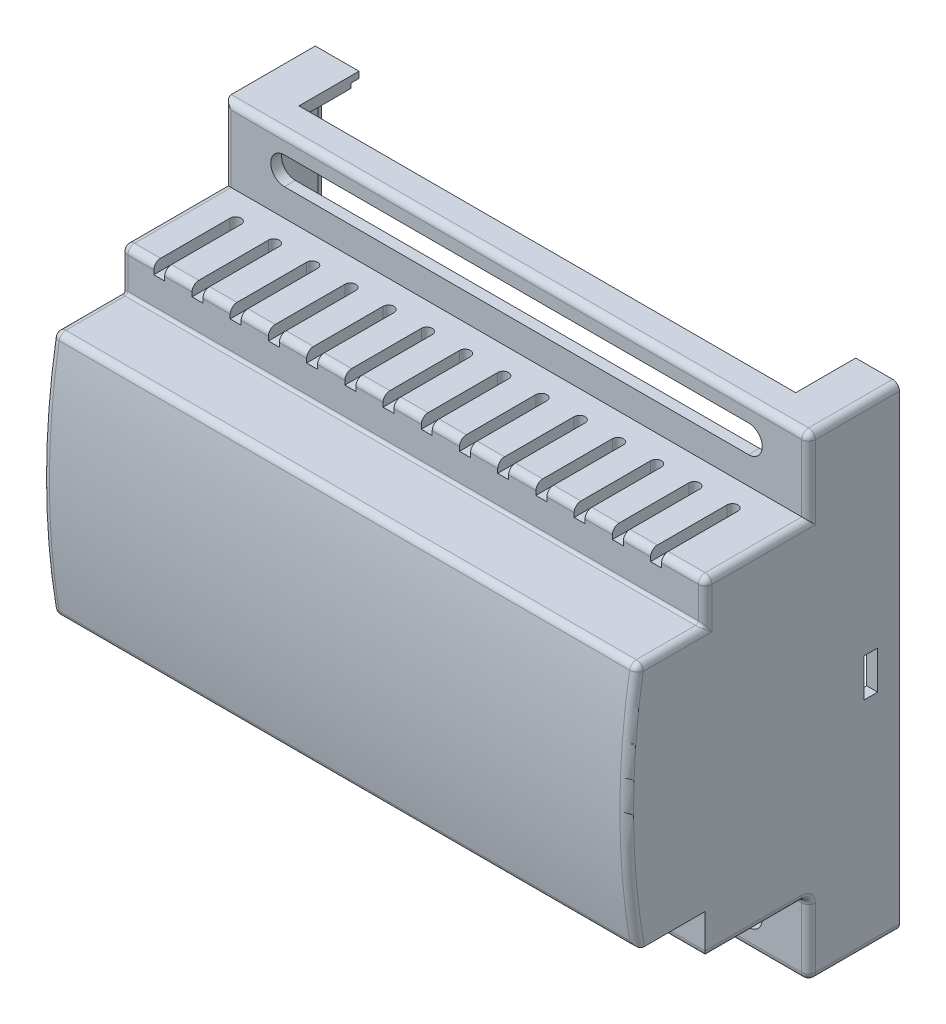
SolidWorks part; units mm, degrees
ref_plane "Alzado" through (0, 0, 0) normal (0, 0, 1) x (1, 0, 0)
ref_plane "Planta" through (0, 0, 0) normal (0, 1, 0) x (1, 0, 0)
ref_plane "Vista lateral" through (0, 0, 0) normal (1, 0, 0) x (0, 0, -1)
sketch "Sketch1" plane through (0, 0, 0) normal (1, 0, 0) x (0, 0, -1)
  line L0 (0, -43.5) -> (0, 43.5)
  line L1 (0, 43.5) -> (-16.65, 43.5)
  line L2 (-16.65, 43.5) -> (-16.65, 30)
  line L3 (-16.65, 30) -> (-35.59, 30)
  line L4 (-35.59, 30) -> (-35.59, 22.5)
  line L5 (-35.59, 22.5) -> (-48, 22.5)
  line L7 (55, 0) -> (-55, 0) construction
  line L8 (-35.59, -22.5) -> (-48, -22.5)
  line L9 (-35.59, -30) -> (-35.59, -22.5)
  line L10 (-16.65, -30) -> (-35.59, -30)
  line L11 (-16.65, -43.5) -> (-16.65, -30)
  line L12 (0, -43.5) -> (-16.65, -43.5)
  arc A1 (-48, 22.5) -> (-48, -22.5) centre (79.6725, 0) ccw
  point P12 (-48, 0)
  point P17 (0, 0)
  dimension "D7" = 259.28
  dimension "D1" = 87
  dimension "D2" = 16.65
  dimension "D3" = 35.59
  dimension "D4" = 48
  dimension "D5" = 60
  dimension "D6" = 45
extrude "Boss-Extrude3" add sketch "Sketch1" along normal blind 107
shell "Shell3" thickness 2 removed face at (53.5, 0, 0)
fillet "Fillet3" radius 1.25 26 edges at (107, 0, 49.9675) (53.5, -22.5, 48) (0, 0, 49.9675) (53.5, 22.5, 48) (107, -36.75, 16.65) (0, -36.75, 16.65) (53.5, -30, 35.59) (107, -30, 26.12) (53.5, -30, 16.65) (0, -30, 26.12) (0, -26.25, 35.59) (0, -22.5, 41.795) (0, 22.5, 41.795) (0, 26.25, 35.59) (0, 30, 26.12) (0, 36.75, 16.65) (53.5, 43.5, 16.65) (107, 43.5, 8.325) (107, 36.75, 16.65) (107, 30, 26.12) (53.5, 30, 35.59) (107, 26.25, 35.59) (107, 22.5, 41.795) (0, -43.5, 8.325) (107, -43.5, 8.325) (53.5, -43.5, 16.65)
sketch "Sketch5" plane through (107, 0, 0) normal (1, 0, 0) x (0, 0, -1)
  line L0 (0, 0) -> (-48.7175, 0) construction
  line L1 (0, -42.25) -> (0, 42.25) construction
  line L2 (-4, 3.5) -> (-6.5, 3.5)
  line L3 (-4, 3.5) -> (-4, -3.5)
  line L4 (-4, -3.5) -> (-6.5, -3.5)
  line L5 (-6.5, 3.5) -> (-6.5, -3.5)
  line L6 (-4, 3.5) -> (-6.5, -3.5) construction
  line L7 (-4, -3.5) -> (-6.5, 3.5) construction
  arc A0 (-46.9467, 21.25) -> (-46.7305, -22.5) centre (79.6725, 0) ccw construction
  point P7 (-5.25, 0)
  point P14 (-5.25, -3.5)
  dimension "D1" = 4
  dimension "D2" = 7
  dimension "D3" = 2.5
extrude "Cut-Extrude3" cut sketch "Sketch5" against normal through all
sketch "Sketch6" plane through (0, -43.5, 0) normal (0, -1, 0) x (1, 0, 0)
  line L0 (105.75, 0) -> (1.25, 0) construction
  line L1 (99, -11) -> (8, -11)
  line L2 (99, -11) -> (99, 11)
  line L3 (99, 11) -> (8, 11)
  line L4 (8, -11) -> (8, 11)
  line L5 (99, -11) -> (8, 11) construction
  line L6 (99, 11) -> (8, -11) construction
  point P0 (53.5, 0)
  dimension "D1" = 91
  dimension "D2" = 11
extrude "Cut-Extrude4" cut sketch "Sketch6" against normal through all
sketch "Sketch7" plane through (0, 0, 16.65) normal (0, 0, 1) x (1, 0, 0)
  line L0 (11, -37.5) -> (96, -37.5) construction
  line L1 (11, -35) -> (96, -35)
  line L2 (11, -40) -> (96, -40)
  line L3 (96, 37.52) -> (11, 37.52) construction
  line L4 (96, 35) -> (11, 35)
  line L5 (96, 40.04) -> (11, 40.04)
  line L6 (53.5, 42.25) -> (53.5, -43.5) construction
  line L7 (105.75, 42.25) -> (1.25, 42.25) construction
  line L8 (105.75, -43.5) -> (1.25, -43.5) construction
  arc A0 (11, -35) -> (11, -40) centre (11, -37.5) ccw
  arc A1 (96, -40) -> (96, -35) centre (96, -37.5) ccw
  arc A2 (96, 35) -> (96, 40.04) centre (96, 37.52) ccw
  arc A3 (11, 40.04) -> (11, 35) centre (11, 37.52) ccw
  point P2 (53.5, -37.5)
  point P10 (53.5, 37.52)
  dimension "D5" = 2.52
  dimension "D6" = 2.5
  dimension "D1" = 85
  dimension "D2" = 35
  dimension "D3" = 85
  dimension "D4" = 35
extrude "Cut-Extrude5" cut sketch "Sketch7" against normal blind 3
fillet "Fillet4" radius 0.5 30 edges at (2, -20.5, 39.9502) (2, -34.75, 14.65) (105, -20.5, 39.9502) (106.6339, 22.1339, 35.2239) (0.3661, 22.1339, 35.2239) (53.5, -20.5, 46.3105) (53.5, 20.5, 46.3105) (53.5, 22.5, 35.59) (53.5, 28, 33.59) (53.5, 28, 14.65) (105, 0, 47.9675) (105, 20.5, 39.9502) (105, 24.25, 33.59) (105, 28, 24.12) (105, 34.75, 14.65) (105, 41.5, 7.325) (2, 41.5, 7.325) (2, 34.75, 14.65) (2, 28, 24.12) (2, 24.25, 33.59) (2, 20.5, 39.9502) (2, 0, 47.9675) (2, -24.25, 33.59) (53.5, -28, 14.65) (105, -34.75, 14.65) (105, -28, 24.12) (105, -24.25, 33.59) (53.5, -28, 33.59) (2, -28, 24.12) (53.5, -20.5, 33.59)
sketch "Sketch8" plane through (0, -30, 0) normal (0, -1, 0) x (1, 0, 0)
  line L0 (107, 35.59) -> (1.25, 35.59) construction
  line L1 (6, 35.59) -> (8, 35.59)
  line L2 (6, 35.59) -> (6, 21.59)
  line L4 (8, 35.59) -> (8, 21.59)
  line L5 (8, 0) -> (1.25, 0) construction
  line L8 (53.5, 49.9675) -> (53.5, 0) construction
  line L9 (105.75, 49.9675) -> (1.25, 49.9675) construction
  line L11 (0, 17.9) -> (0, 34.34) construction
  line L12 (13, 35.59) -> (13, 21.59)
  line L13 (15, 35.59) -> (15, 21.59)
  line L14 (13, 35.59) -> (15, 35.59)
  line L15 (20, 35.59) -> (20, 21.59)
  line L16 (22, 35.59) -> (22, 21.59)
  line L17 (20, 35.59) -> (22, 35.59)
  line L18 (27, 35.59) -> (27, 21.59)
  line L19 (29, 35.59) -> (29, 21.59)
  line L20 (27, 35.59) -> (29, 35.59)
  line L21 (34, 35.59) -> (34, 21.59)
  line L22 (36, 35.59) -> (36, 21.59)
  line L23 (34, 35.59) -> (36, 35.59)
  line L24 (41, 35.59) -> (41, 21.59)
  line L25 (43, 35.59) -> (43, 21.59)
  line L26 (41, 35.59) -> (43, 35.59)
  line L27 (48, 35.59) -> (48, 21.59)
  line L28 (50, 35.59) -> (50, 21.59)
  line L29 (48, 35.59) -> (50, 35.59)
  line L30 (55, 35.59) -> (55, 21.59)
  line L31 (57, 35.59) -> (57, 21.59)
  line L32 (55, 35.59) -> (57, 35.59)
  line L33 (62, 35.59) -> (62, 21.59)
  line L34 (64, 35.59) -> (64, 21.59)
  line L35 (62, 35.59) -> (64, 35.59)
  line L36 (69, 35.59) -> (69, 21.59)
  line L37 (71, 35.59) -> (71, 21.59)
  line L38 (69, 35.59) -> (71, 35.59)
  line L39 (76, 35.59) -> (76, 21.59)
  line L40 (78, 35.59) -> (78, 21.59)
  line L41 (76, 35.59) -> (78, 35.59)
  line L42 (83, 35.59) -> (83, 21.59)
  line L43 (85, 35.59) -> (85, 21.59)
  line L44 (83, 35.59) -> (85, 35.59)
  line L45 (90, 35.59) -> (90, 21.59)
  line L46 (92, 35.59) -> (92, 21.59)
  line L47 (90, 35.59) -> (92, 35.59)
  line L48 (97, 35.59) -> (97, 21.59)
  line L49 (99, 35.59) -> (99, 21.59)
  line L50 (97, 35.59) -> (99, 35.59)
  arc A0 (6, 21.59) -> (8, 21.59) centre (7, 21.59) ccw
  arc A1 (13, 21.59) -> (15, 21.59) centre (14, 21.59) ccw
  arc A2 (20, 21.59) -> (22, 21.59) centre (21, 21.59) ccw
  arc A3 (27, 21.59) -> (29, 21.59) centre (28, 21.59) ccw
  arc A4 (34, 21.59) -> (36, 21.59) centre (35, 21.59) ccw
  arc A5 (41, 21.59) -> (43, 21.59) centre (42, 21.59) ccw
  arc A6 (48, 21.59) -> (50, 21.59) centre (49, 21.59) ccw
  arc A7 (55, 21.59) -> (57, 21.59) centre (56, 21.59) ccw
  arc A8 (62, 21.59) -> (64, 21.59) centre (63, 21.59) ccw
  arc A9 (69, 21.59) -> (71, 21.59) centre (70, 21.59) ccw
  arc A10 (76, 21.59) -> (78, 21.59) centre (77, 21.59) ccw
  arc A11 (83, 21.59) -> (85, 21.59) centre (84, 21.59) ccw
  arc A12 (90, 21.59) -> (92, 21.59) centre (91, 21.59) ccw
  arc A13 (97, 21.59) -> (99, 21.59) centre (98, 21.59) ccw
  point P17 (6, 28.59)
  dimension "D1" = 1
  dimension "D2" = 21.59
  dimension "D3" = 6
  dimension "D4" = 14
extrude "Cut-Extrude7" cut sketch "Sketch8" against normal blind 2
mirror "Mirror1" about plane through (0, 0, 0) normal (0, 1, 0) of "Cut-Extrude7"
sketch "Sketch10" plane through (0, 0, 0) normal (0, 0, -1) x (-1, 0, 0)
  line L8 (-107, -42.25) -> (-107, 42.25) construction
  line L9 (-105.85, 42.35) -> (-1.15, 42.35)
  line L10 (-105.85, 42.35) -> (-105.85, -42.35)
  line L11 (-105.85, -42.35) -> (-1.15, -42.35)
  line L12 (-1.15, 42.35) -> (-1.15, -42.35)
  line L13 (0, -42.25) -> (0, 43.5) construction
  line L14 (-105.75, 43.5) -> (-99, 43.5) construction
  line L15 (-105.75, -43.5) -> (-99, -43.5) construction
  dimension "D1" = 1.15
  dimension "D2" = 1.15
  dimension "D3" = 1.15
  dimension "D4" = 1.15
extrude "Cut-Extrude8" cut sketch "Sketch10" against normal blind 1.5
fillet "Fillet5" radius 0.5 7 edges at (105, -41.5, 7.825) (104.8536, -41.5, 14.5036) (53.5, -41.5, 14.65) (2.1464, -41.5, 14.5036) (1.15, -42.35, 0.75) (2, -41.5, 7.825) (105.85, -42.35, 0.75)
